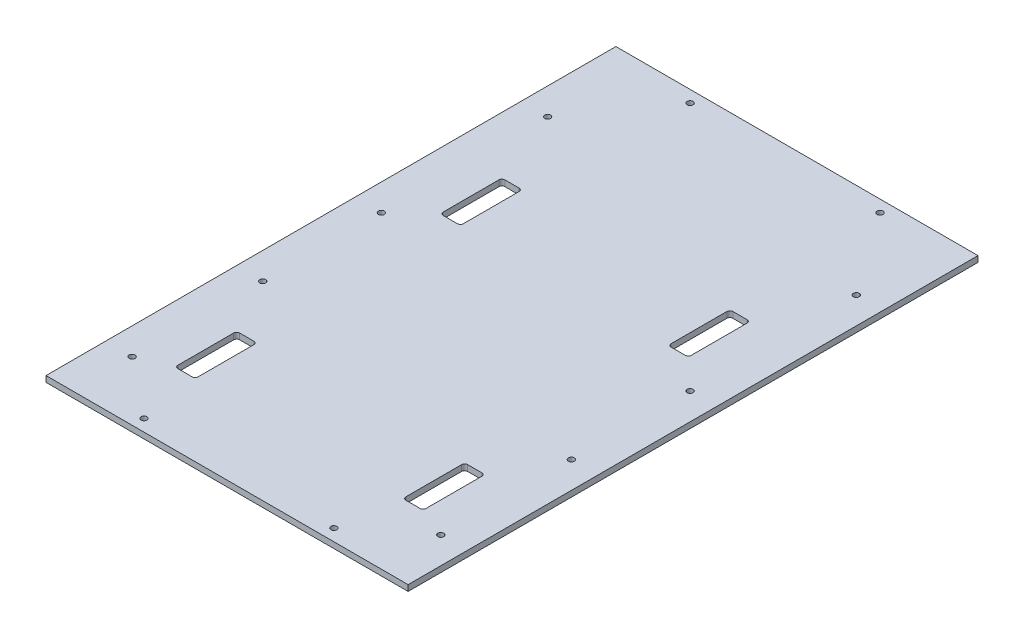
SolidWorks part; units mm, degrees
ref_plane "Front Plane" through (0, 0, 0) normal (0, 0, 1) x (1, 0, 0)
ref_plane "Top Plane" through (0, 0, 0) normal (0, 1, 0) x (1, 0, 0)
ref_plane "Right Plane" through (0, 0, 0) normal (1, 0, 0) x (0, 0, -1)
sketch "Sketch1" plane through (0, 0, 0) normal (0, 1, 0) x (1, 0, 0)
  line L1 (-193.675, -304.8) -> (193.675, -304.8)
  line L2 (-193.675, -304.8) -> (-193.675, 304.8)
  line L3 (-193.675, 304.8) -> (193.675, 304.8)
  line L4 (193.675, -304.8) -> (193.675, 304.8)
  line L5 (0, 304.8) -> (0, -304.8) construction
  line L6 (-193.675, 0) -> (193.675, 0) construction
  point P0 (0, 0)
  dimension "D1" = 387.35
  dimension "D2" = 609.6
extrude "Boss-Extrude1" add sketch "Sketch1" along normal blind 6.35
sketch "Sketch2" plane through (0, 6.35, 0) normal (0, 1, 0) x (1, 0, 0)
  line L0 (0, -1000) -> (0, 49000) construction
  line L6 (111.125, -227.838) -> (132.715, -227.838)
  line L7 (111.125, 55.88) -> (132.715, 55.88)
  line L8 (111.125, 55.88) -> (111.125, 121.92)
  line L9 (111.125, 121.92) -> (132.715, 121.92)
  line L10 (132.715, 55.88) -> (132.715, 121.92)
  line L11 (121.92, 121.92) -> (121.92, 55.88) construction
  line L12 (111.125, 88.9) -> (132.715, 88.9) construction
  line L17 (111.125, -227.838) -> (111.125, -161.798)
  line L18 (111.125, -161.798) -> (132.715, -161.798)
  line L23 (132.715, -227.838) -> (132.715, -161.798)
  line L24 (121.92, -161.798) -> (121.92, -227.838) construction
  line L25 (111.125, -194.818) -> (132.715, -194.818) construction
  line L26 (-121.92, -161.798) -> (-121.92, -227.838) construction
  line L27 (-132.715, -227.838) -> (-132.715, -161.798)
  line L28 (-111.125, -227.838) -> (-111.125, -161.798)
  line L29 (-111.125, -227.838) -> (-132.715, -227.838)
  line L30 (-111.125, -194.818) -> (-132.715, -194.818) construction
  line L31 (-111.125, -161.798) -> (-132.715, -161.798)
  line L32 (-111.125, 88.9) -> (-132.715, 88.9) construction
  line L33 (-121.92, 121.92) -> (-121.92, 55.88) construction
  line L34 (-132.715, 55.88) -> (-132.715, 121.92)
  line L35 (-111.125, 121.92) -> (-132.715, 121.92)
  line L36 (-111.125, 55.88) -> (-111.125, 121.92)
  line L37 (-111.125, 55.88) -> (-132.715, 55.88)
  line L38 (193.675, 304.8) -> (-193.675, 304.8) construction
  point P1 (121.92, -194.818)
  point P4 (121.92, 88.9)
  point P20 (-121.92, -194.818)
  point P29 (-121.92, 88.9)
  dimension "D1" = 66.04
  dimension "D2" = 21.59
  dimension "D3" = 66.04
  dimension "D4" = 283.718
  dimension "D5" = 215.9
  dimension "D6" = 121.92
extrude "Cut-Extrude1" cut sketch "Sketch2" against normal through all
fillet "Fillet1" radius 3.175 16 edges at (-132.715, 3.175, -121.92) (-111.125, 3.175, -121.92) (132.715, 3.175, 227.838) (132.715, 3.175, 161.798) (111.125, 3.175, 161.798) (111.125, 3.175, 227.838) (-111.125, 3.175, 227.838) (-132.715, 3.175, 227.838) (-111.125, 3.175, 161.798) (-132.715, 3.175, 161.798) (132.715, 3.175, -55.88) (111.125, 3.175, -55.88) (132.715, 3.175, -121.92) (111.125, 3.175, -121.92) (-111.125, 3.175, -55.88) (-132.715, 3.175, -55.88)
ref_plane "front_wheel" through (0, 0, -88.9) normal (0, 0, 1) x (1, 0, 0)
ref_plane "back_wheel" through (0, 0, 194.818) normal (0, 0, 1) x (1, 0, 0)
ref_plane "stream_midplane" through (0, 0, 0) normal (0, 0, 1) x (1, 0, 0)
sketch "Sketch3" plane through (0, 0, 0) normal (0, -1, 0) x (-1, 0, 0)
  line L0 (-193.675, 304.8) -> (193.675, 304.8) construction
  line L3 (-3.4925, 0) -> (3.4925, 0) construction
  line L4 (193.675, -304.8) -> (-193.675, -304.8) construction
  line L5 (0, 3.4925) -> (0, -3.4925) construction
  line L6 (-3.4925, 0) -> (3.4925, 0) construction
  circle A0 centre (101.6, 292.1) radius 3.175
  circle A1 centre (165.1, 203.2) radius 3.175
  circle A2 centre (165.1, -101.6) radius 3.175
  circle A3 centre (165.1, 25.4) radius 3.175
  circle A5 centre (165.1, -241.3) radius 3.175
  circle A6 centre (-165.1, -241.3) radius 3.175
  circle A7 centre (-165.1, -101.6) radius 3.175
  circle A8 centre (-165.1, 25.4) radius 3.175
  circle A9 centre (-165.1, 203.2) radius 3.175
  circle A10 centre (-101.6, 292.1) radius 3.175
  circle A11 centre (101.6, -292.1) radius 3.175
  circle A12 centre (-101.6, -292.1) radius 3.175
  dimension "D1" = 6.35
  dimension "D2" = 6.35
  dimension "D6" = 6.35
  dimension "D10" = 6.35
  dimension "D3" = 12.7
  dimension "D4" = 165.1
  dimension "D5" = 101.6
  dimension "D7" = 101.6
  dimension "D9" = 101.6
  dimension "D8" = 25.4
  dimension "D11" = 63.5
  dimension "D12" = 165.1
extrude "Cut-Extrude2" cut sketch "Sketch3" against normal through all
